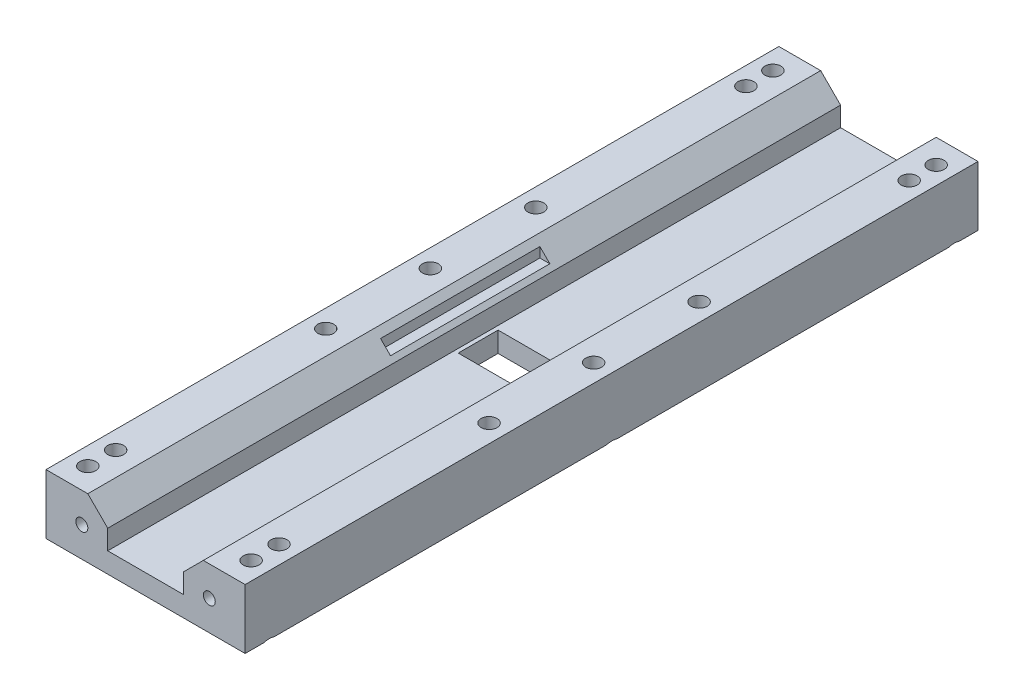
SolidWorks part; units mm, degrees
ref_plane "Plan de face" through (0, 0, 0) normal (0, 0, 1) x (1, 0, 0)
ref_plane "Plan de dessus" through (0, 0, 0) normal (0, 1, 0) x (1, 0, 0)
ref_plane "Plan de droite" through (0, 0, 0) normal (1, 0, 0) x (0, 0, -1)
sketch "Esquisse1" plane through (0, 0, 0) normal (0, 0, 1) x (1, 0, 0)
  line L0 (0, 23.083) -> (50, 23.083) construction
  line L1 (0, 0) -> (50, 0)
  line L2 (0, 0) -> (0, 46.166) construction
  line L3 (0, 46.166) -> (50, 46.166) construction
  line L4 (50, 0) -> (50, 46.166) construction
  line L5 (0, 15) -> (10.5, 15)
  line L6 (15.5, 10) -> (15.5, 5.083)
  line L7 (50, 15) -> (39.5, 15)
  line L8 (34.5, 10) -> (34.5, 5.083)
  line L9 (13, 33.666) -> (37, 12.5) construction
  line L10 (15.5, 5.083) -> (34.5, 5.083)
  line L11 (0, 15) -> (0, 0)
  line L12 (50, 15) -> (50, 0)
  line L13 (10.5, 15) -> (15.5, 10)
  line L14 (39.5, 15) -> (34.5, 10)
  line L15 (25, 23.083) -> (13, 12.5) construction
  circle A0 centre (25, 23.083) radius 16 construction
  dimension "D1" = 50
  dimension "D5" = 18
  dimension "D4" = 32
  dimension "D2" = 5
  dimension "D3" = 5
  dimension "D6" = 15
  dimension "D7" = 10.5
  dimension "D8" = 10.5
extrude "Boss.-Extru.1" add sketch "Esquisse1" along normal blind 184
sketch "Esquisse2" plane through (0, 15, 0) normal (0, 1, 0) x (-1, 0, 0)
  line L0 (0, 184) -> (0, 0) construction
  line L1 (-10.5, 0) -> (0, 0) construction
  line L2 (-10.5, 184) -> (0, 184) construction
  line L3 (-50, 184) -> (-50, 0) construction
  circle A0 centre (-4.5, 12.78) radius 2
  circle A1 centre (-45.5, 12.78) radius 2
  circle A2 centre (-4.5, 65.52) radius 2
  circle A3 centre (-45.5, 65.52) radius 2
  circle A4 centre (-4.5, 118.26) radius 2
  circle A5 centre (-45.5, 118.26) radius 2
  circle A6 centre (-4.5, 171) radius 2
  circle A7 centre (-45.5, 171) radius 2
  dimension "D2" = 4
  dimension "D1" = 4.5
  dimension "D3" = 12.78
  dimension "D6" = 13
  dimension "D7" = 4.5
  dimension "D8" = 4.5
  dimension "D4" = 2
  dimension "D5" = 4
extrude "Enlèv. mat.-Extru.1" cut sketch "Esquisse2" against normal blind 205.56
sketch "Esquisse4" plane through (0, 15, 0) normal (0, 1, 0) x (-1, 0, 0)
  line L0 (-10.5, 0) -> (0, 0) construction
  line L1 (0, 184) -> (0, 0) construction
  line L2 (-50, 184) -> (-50, 0) construction
  line L3 (-50, 0) -> (-39.5, 0) construction
  line L5 (-50, 184) -> (-39.5, 184) construction
  line L6 (-10.5, 184) -> (0, 184) construction
  line L7 (0, 92) -> (-50, 92) construction
  circle A0 centre (-4.5, 6) radius 2
  circle A1 centre (-45.5, 6) radius 2
  circle A2 centre (-45.5, 178) radius 2
  circle A3 centre (-4.5, 178) radius 2
  circle A4 centre (-4.5, 92) radius 2
  circle A5 centre (-45.5, 92) radius 2
  dimension "D1" = 4
  dimension "D4" = 4.5
  dimension "D5" = 4
  dimension "D7" = 4
  dimension "D8" = 4
  dimension "D13" = 4
  dimension "D14" = 4
  dimension "D16" = 4.5
  dimension "D2" = 6
  dimension "D3" = 4.5
  dimension "D6" = 6
  dimension "D9" = 4.5
  dimension "D10" = 4.5
  dimension "D11" = 6
  dimension "D12" = 6
  dimension "D15" = 4.5
extrude "Enlèv. mat.-Extru.2" cut sketch "Esquisse4" against normal blind 205.56
chamfer "Chanfrein1" distance 2.7 angle 45 6 edges at (45.5, 0, 94) (4.5, 0, 94) (45.5, 0, 8) (4.5, 0, 8) (4.5, 0, 180) (45.5, 0, 180)
sketch "Esquisse6" plane through (0, 15, 0) normal (0, 1, 0) x (1, 0, 0)
  line L0 (15.5, -92) -> (34.5, -92) construction
  line L1 (15.5, -184) -> (15.5, 0) construction
  line L2 (34.5, -184) -> (34.5, 0) construction
  line L3 (25, -72) -> (25, -112) construction
  line L4 (12, -72) -> (38, -72)
  line L5 (12, -72) -> (12, -112)
  line L6 (12, -112) -> (38, -112)
  line L7 (38, -72) -> (38, -112)
  line L8 (25, -112) -> (25, -72) construction
  line L9 (0, -184) -> (0, 0) construction
  dimension "D1" = 26
  dimension "D2" = 25
  dimension "D3" = 20
  dimension "D4" = 20
extrude "Enlèv. mat.-Extru.3" cut sketch "Esquisse6" against normal blind 4
sketch "Esquisse8" plane through (0, 5.083, 0) normal (0, 1, 0) x (1, 0, 0)
  line L0 (15.5, -184) -> (15.5, 0) construction
  line L1 (16.5, -87) -> (33.5, -87)
  line L2 (16.5, -87) -> (16.5, -97)
  line L3 (16.5, -97) -> (33.5, -97)
  line L4 (33.5, -87) -> (33.5, -97)
  line L5 (34.5, -72) -> (34.5, -112) construction
  line L6 (34.5, -112) -> (38, -112) construction
  line L7 (38, -72) -> (34.5, -72) construction
  point P8 (36.25, -112)
  point P11 (36.25, -72)
  dimension "D1" = 1
  dimension "D2" = 1
  dimension "D3" = 15
  dimension "D4" = 15
extrude "Enlèv. mat.-Extru.6" cut sketch "Esquisse8" against normal blind 10
sketch "Esquisse7" plane through (0, 0, 184) normal (0, 0, 1) x (1, 0, 0)
  line L0 (0, 0) -> (50, 0) construction
  line L1 (0, 15) -> (0, 0) construction
  line L2 (50, 0) -> (50, 15) construction
  circle A0 centre (9, 7.5) radius 1.5
  circle A1 centre (41, 7.5) radius 1.5
  dimension "D1" = 3
  dimension "D2" = 3
  dimension "D3" = 7.5
  dimension "D4" = 9
  dimension "D5" = 9
  dimension "D6" = 7.5
extrude "Enlèv. mat.-Extru.5" cut sketch "Esquisse7" against normal blind 5
sketch "Esquisse9" plane through (0, 0, 0) normal (0, 0, -1) x (-1, 0, 0)
  line L0 (0, 0) -> (-50, 0) construction
  line L1 (-50, 0) -> (-50, 15) construction
  line L2 (0, 15) -> (0, 0) construction
  circle A0 centre (-42.5, 7.5) radius 1.5
  circle A1 centre (-7.5, 7.5) radius 1.5
  dimension "D1" = 3
  dimension "D2" = 3
  dimension "D3" = 7.5
  dimension "D4" = 7.5
  dimension "D5" = 7.5
  dimension "D6" = 7.5
extrude "Enlèv. mat.-Extru.10" cut sketch "Esquisse9" against normal blind 5
